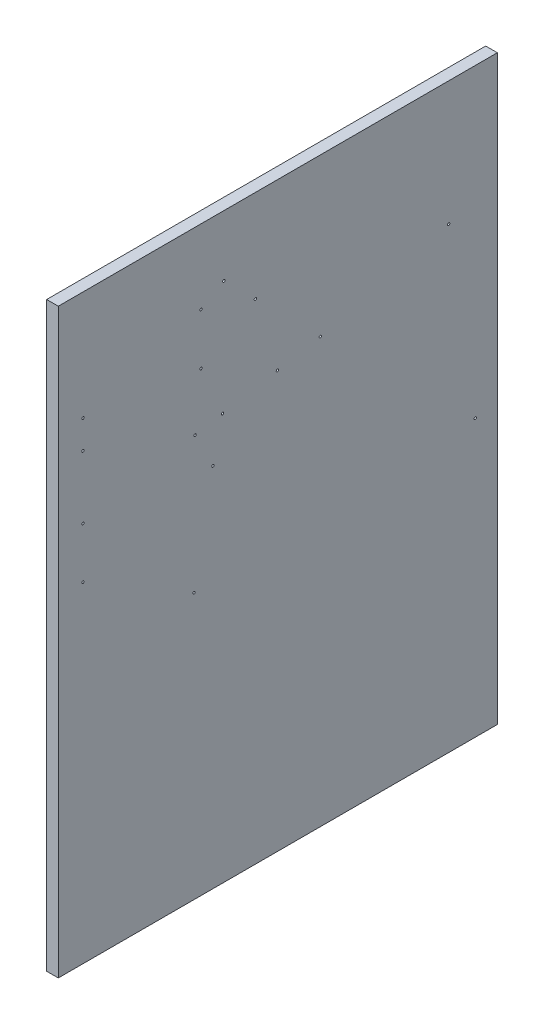
SolidWorks part; units mm, degrees
ref_plane "Спереди" through (0, 0, 0) normal (0, 0, 1) x (1, 0, 0)
ref_plane "Сверху" through (0, 0, 0) normal (0, 1, 0) x (1, 0, 0)
ref_plane "Справа" through (0, 0, 0) normal (1, 0, 0) x (0, 0, -1)
sketch "Эскиз1" plane through (0, 0, 0) normal (1, 0, 0) x (0, 0, -1)
  line L1 (-74.5221, 423.7162) -> (491.4779, 423.7162)
  line L2 (-74.5221, 423.7162) -> (-74.5221, -326.2838)
  line L3 (-74.5221, -326.2838) -> (491.4779, -326.2838)
  line L4 (491.4779, 423.7162) -> (491.4779, -326.2838)
  dimension "D1" = 566
  dimension "D2" = 750
extrude "Бобышка-Вытянуть1" add sketch "Эскиз1" along normal blind 15
sketch "Эскиз3" plane through (0, 0, 0) normal (-1, 0, 0) x (0, 0, 1)
  circle A0 centre (-459.1211, 408.987) radius 4
extrude "Вырез-Вытянуть1" cut sketch "Эскиз3" against normal blind 10
sketch "Эскиз4" plane through (0, 0, 0) normal (-1, 0, 0) x (0, 0, 1)
  line L0 (-491.4779, 345.2356) -> (71.2158, 345.2356) construction
  line L1 (-491.4779, -326.2838) -> (-491.4779, 423.7162) construction
  line L2 (-208.4779, 423.7162) -> (-208.4779, -326.2838) construction
  line L3 (-491.4779, 423.7162) -> (74.5221, 423.7162) construction
  line L4 (74.5221, -326.2838) -> (-491.4779, -326.2838) construction
  line L5 (-138.8455, 423.7162) -> (-138.9099, 345.2356) construction
  line L6 (-138.9099, 345.2356) -> (-263.2761, 220.8694) construction
  line L7 (-179.4956, 423.7162) -> (-179.4956, 304.6499) construction
  line L8 (-263.2761, 220.8694) -> (-263.2761, 423.7162) construction
  line L9 (-263.2761, 220.8694) -> (-432.2169, 51.9286) construction
  line L10 (-273.2861, 210.8594) -> (74.5221, 210.8594) construction
  line L11 (-207.9311, 210.8594) -> (74.5221, 159.4945) construction
  line L12 (74.5221, 423.7162) -> (74.5221, -326.2838) construction
  line L13 (-137.1199, 197.9822) -> (-137.1199, 210.8594) construction
  line L14 (42.7147, 165.2788) -> (42.7147, 210.8594) construction
  line L15 (-207.9311, 210.8594) -> (-263.2298, 220.9157) construction
  line L16 (42.7147, 165.2788) -> (-124.8312, 145.7156) construction
  line L17 (-124.8312, 145.7156) -> (42.7147, 99.6926) construction
  line L18 (42.7147, 99.6926) -> (-100.411, 16.3608) construction
  line L19 (-101.7897, 191.5573) -> (-101.7897, 210.8594) construction
  line L20 (-101.7897, 191.5573) -> (42.7147, 246.3014) construction
  line L21 (42.7147, 246.3014) -> (-428.8213, 263.704) construction
  line L22 (-428.8213, 263.704) -> (42.7147, 282.8725) construction
  line L23 (42.7147, 282.8725) -> (-109.4447, 262.0616) construction
  line L24 (-109.4447, 262.0616) -> (-109.4447, 327.9748) construction
  line L25 (-109.4447, 327.9748) -> (66.9272, 331.7313) construction
  line L26 (-432.2169, 51.9286) -> (-463.0129, 29.9661) construction
  line L27 (-491.4779, 0) -> (74.5221, 0) construction
  circle A0 centre (-138.9099, 345.2356) radius 1.5
  circle A1 centre (-179.4956, 304.6499) radius 1.5
  circle A2 centre (-263.2761, 220.8694) radius 1.5
  circle A3 centre (-207.9311, 210.8594) radius 1.5
  circle A4 centre (-137.1199, 197.9822) radius 1.5
  circle A5 centre (42.7147, 165.2788) radius 1.5
  circle A6 centre (-124.8312, 145.7156) radius 1.5
  circle A7 centre (42.7147, 99.6926) radius 1.5
  circle A8 centre (-100.411, 16.3608) radius 1.5
  circle A9 centre (-101.7897, 191.5573) radius 1.5
  circle A10 centre (42.7147, 246.3014) radius 1.5
  circle A11 centre (-428.8213, 263.704) radius 1.5
  circle A12 centre (42.7147, 282.8725) radius 1.5
  circle A13 centre (-109.4447, 262.0616) radius 1.5
  circle A14 centre (-109.4447, 327.9748) radius 1.5
  circle A15 centre (-463.0129, 29.9661) radius 1.5
  dimension "D1" = 326.2838
extrude "Вырез-Вытянуть2" cut sketch "Эскиз4" against normal through all and the other way through all contours A0 | A1 | A2 | A3 | A4 | A5 | A6 | A7 | A8 | A9 | A10 | A12 | A11 | A13 | A14 | A15
